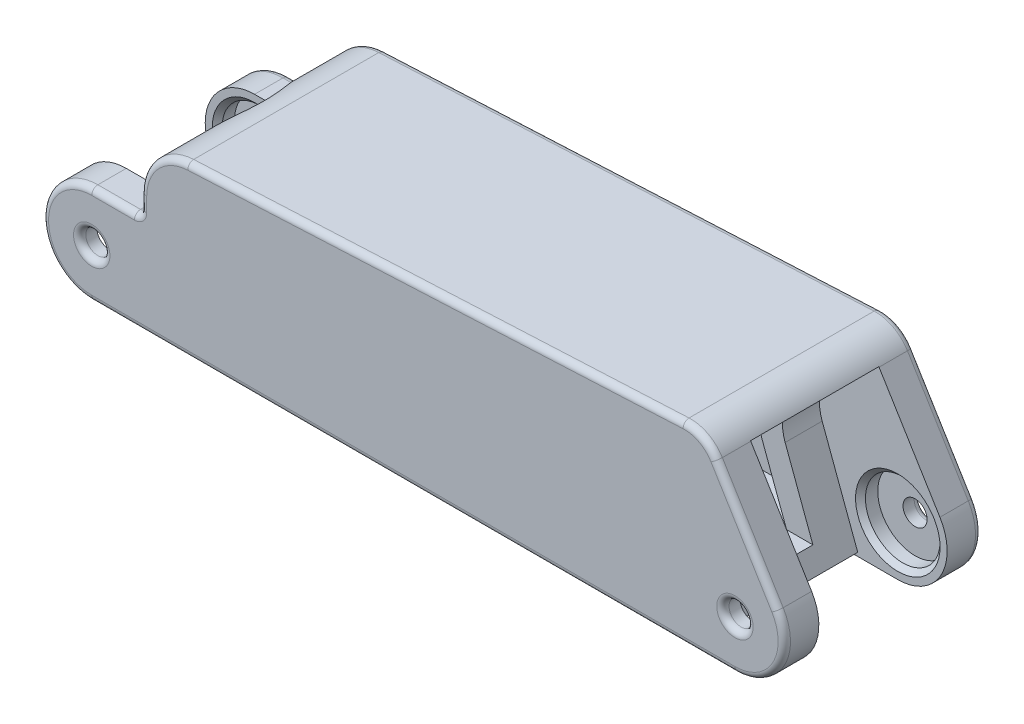
SolidWorks part; units mm, degrees
ref_plane "前视基准面" through (0, 0, 0) normal (0, 0, 1) x (1, 0, 0)
ref_plane "上视基准面" through (0, 0, 0) normal (0, 1, 0) x (1, 0, 0)
ref_plane "右视基准面" through (0, 0, 0) normal (1, 0, 0) x (0, 0, -1)
sketch "草图1" plane through (0, 0, 0) normal (0, 0, 1) x (1, 0, 0)
  line L10 (0, 0) -> (7.9583, 5.6673) construction
  line L11 (7.9583, 5.6673) -> (48.0618, 8.5912) construction
  line L12 (48.0618, 8.5912) -> (52.14, 0) construction
  line L13 (52.14, 0) -> (0, 0) construction
  line L14 (0, -4) -> (52.14, -4)
  line L15 (50.6217, 10.1555) -> (55.5531, 2.0858)
  line L16 (7.7667, 9.6627) -> (47.9182, 11.5878)
  line L20 (0, 4) -> (3.9583, 4)
  line L21 (3.9583, 5.6673) -> (3.9583, 4)
  arc A9 (0, 4) -> (0, -4) centre (0, 0) ccw
  arc A10 (7.7667, 9.6627) -> (3.9583, 5.6673) centre (7.9583, 5.6673) ccw
  arc A11 (50.6217, 10.1555) -> (47.9182, 11.5878) centre (48.0618, 8.5912) ccw
  arc A12 (52.14, -4) -> (55.5531, 2.0858) centre (52.14, 0) ccw
  dimension "D9" = 8
  dimension "D10" = 8
  dimension "D11" = 6
  dimension "D12" = 8
  dimension "D13" = 52.14
  dimension "D14" = 40.21
  dimension "D15" = 9.51
  dimension "D16" = 9.77
extrude "凸台-拉伸1" add sketch "草图1" along normal blind 8 and the other way blind 8
sketch "草图2" plane through (0, 0, 0) normal (0, 0, 1) x (1, 0, 0)
  line L0 (2.7297, -5.5668) -> (0, 0) construction
  line L1 (2.7297, -5.5668) -> (49.7599, 6.1592) construction
  line L2 (-1.5288, -3.6963) -> (0.0361, -6.8876)
  line L3 (-0.12, -22.8543) -> (51.9611, -22.8543) construction
  line L4 (-0.12, -22.8543) -> (12.3687, -25.0564) construction
  line L5 (55.5531, 2.0858) -> (50.6217, 10.1555) construction
  line L6 (3.9583, 4) -> (0, 4) construction
  line L7 (55.5531, 2.0858) -> (52.7003, 6.7541)
  line L8 (3.45, 4) -> (0, 4)
  line L11 (0, -4) -> (52.14, -4) construction
  line L12 (7.1667, -4) -> (52.14, -4)
  arc A0 (0.0361, -6.8876) -> (5.4785, -6.7683) centre (2.7297, -5.5668) ccw
  arc A2 (52.7003, 6.7541) -> (49.8235, 9.1585) centre (49.7599, 6.1592) ccw
  arc A3 (49.8235, 9.1585) -> (3.45, 4) centre (46.0635, -168.0616) ccw
  arc A4 (7.1667, -4) -> (5.4785, -6.7683) centre (16.474, -11.5745) ccw
  circle A6 centre (52.14, 0) radius 0.9969 construction
  arc A7 (52.14, -4) -> (55.5531, 2.0858) centre (52.14, 0) ccw construction
  arc A8 (52.14, -4) -> (55.5531, 2.0858) centre (52.14, 0) ccw
  arc A9 (0, 4) -> (-1.5288, -3.6963) centre (0, 0) ccw
  dimension "D2" = 6
  dimension "D3" = 6
  dimension "D6" = 24
  dimension "D7" = 177.26
  dimension "D8" = 0
  dimension "D11" = 6.6031
  dimension "D4" = 48.47
  dimension "D5" = 6.2
  dimension "D9" = 10
  dimension "D10" = 24
extrude "切除-拉伸1" cut sketch "草图2" against normal blind 2.2 and the other way blind 2.2
sketch "草图3" plane through (0, 0, 0) normal (0, 0, 1) x (1, 0, 0)
  circle A0 centre (0, 0) radius 0.975
  circle A1 centre (52.14, 0) radius 0.975
  dimension "D1" = 1.95
  dimension "D2" = 1.95
extrude "切除-拉伸2" cut sketch "草图3" against normal through all both and the other way through all
sketch "草图4" plane through (0, 4, 0) normal (0, 1, 0) x (1, 0, 0)
  line L0 (0, 0) -> (6, 0) construction
  line L5 (-2.9933, 5.2) -> (2.9933, 5.2)
  line L6 (-2.9933, -5.2) -> (2.9933, -5.2)
  line L7 (-2.9933, 5.2) -> (-6.8366, 5.2)
  line L8 (-6.8366, 5.2) -> (-6.8366, -5.2)
  line L9 (-6.8366, -5.2) -> (-2.9933, -5.2)
  arc A0 (-2.9933, 5.2) -> (-2.9933, -5.2) centre (0, 0) ccw construction
  arc A1 (2.9933, -5.2) -> (2.9933, 5.2) centre (0, 0) ccw
  dimension "D1" = 12
  dimension "D2" = 5.2
  dimension "D3" = 10.4
extrude "切除-拉伸5" cut sketch "草图4" against normal through all both and the other way through all
sketch "草图5" plane through (0, 0, 0) normal (0, 0, 1) x (1, 0, 0)
  line L0 (52.14, 0) -> (87.14, 0) construction
  line L1 (49.2899, 5.2799) -> (52.14, 0) construction
  line L2 (46.65, 3.8549) -> (49.5001, -1.425) construction
  line L4 (49.6265, 8.2609) -> (87.5888, 3.9747) construction
  line L5 (52.14, -4) -> (49.0005, -4)
  line L8 (46.21, 3.6173) -> (49.0601, -1.6625) construction
  line L11 (47.4649, 8.2664) -> (50.6039, 10.1846)
  line L12 (49.6826, 8.7578) -> (87.6449, 4.4716) construction
  line L13 (55.5531, 2.0858) -> (50.6217, 10.1555) construction
  line L14 (55.5531, 2.0858) -> (50.6039, 10.1846)
  line L17 (0, -4) -> (52.14, -4) construction
  line L18 (46.0086, 4.0622) -> (49.0005, -4)
  arc A0 (49.5001, -1.425) -> (52.0543, -2.9988) centre (52.14, 0) ccw construction
  arc A1 (49.6265, 8.2609) -> (46.65, 3.8549) centre (49.2899, 5.2799) ccw construction
  arc A2 (87.0257, -3.9984) -> (87.5888, 3.9747) centre (87.14, 0) ccw construction
  circle A3 centre (52.14, 0) radius 0.975 construction
  arc A4 (52.14, -4) -> (55.5531, 2.0858) centre (52.14, 0) ccw construction
  arc A5 (52.14, -4) -> (55.5531, 2.0858) centre (52.14, 0) ccw
  arc A6 (47.4649, 8.2664) -> (46.0086, 4.0622) centre (49.2899, 5.2799) ccw
  arc A9 (49.0601, -1.6625) -> (52.04, -3.4986) centre (52.14, 0) ccw construction
  arc A10 (49.6826, 8.7578) -> (46.21, 3.6173) centre (49.2899, 5.2799) ccw construction
  dimension "D2" = 6
  dimension "D3" = 6
  dimension "D4" = 8
  dimension "D7" = 0
  dimension "D1" = 6
  dimension "D5" = 35
  dimension "D6" = 118.36
  dimension "D9" = 8
  dimension "D8" = 0.5
extrude "切除-拉伸6" cut sketch "草图5" against normal blind 5.2 and the other way blind 5.2
sketch "草图6" plane through (0, 0, -5.2) normal (0, 0, 1) x (1, 0, 0)
  circle A0 centre (0, 0) radius 3.025
  dimension "D1" = 6.05
extrude "切除-拉伸7" cut sketch "草图6" against normal blind 1.4
sketch "草图7" plane through (0, 0, -5.2) normal (0, 0, 1) x (1, 0, 0)
  circle A0 centre (52.14, 0) radius 3.025
  dimension "D1" = 6.05
extrude "切除-拉伸8" cut sketch "草图7" against normal blind 1.4
sketch "草图9" plane through (0, 0, 2.2) normal (0, 0, -1) x (-1, 0, 0)
  line L10 (-7.5821, -2) -> (-7.5821, 2.9216)
  line L11 (-7.5821, -2) -> (-7.5821, 2.9216)
  line L12 (-44.1336, 3.3663) -> (-46.125, -2)
  line L13 (-46.125, -2) -> (-7.5821, -2)
  line L14 (-46.125, -2) -> (-7.5821, -2)
  line L15 (-44.1336, 3.3663) -> (-46.125, -2)
  arc A4 (-7.5821, 2.9216) -> (-44.1314, 7.1877) centre (-46.0635, -168.0616) ccw
  arc A5 (-44.1336, 3.3663) -> (-44.1314, 7.1877) centre (-49.2899, 5.2799) ccw
  arc A6 (-7.5821, 2.9216) -> (-44.1314, 7.1877) centre (-46.0635, -168.0616) ccw
  arc A7 (-44.1336, 3.3663) -> (-44.1314, 7.1877) centre (-49.2899, 5.2799) ccw
  dimension "D1" = 2
extrude "切除-拉伸10" cut sketch "草图9" against normal blind 3.2
mirror "镜向1" about plane through (0, 0, 0) normal (0, 0, 1) of "切除-拉伸10", "切除-拉伸7", "切除-拉伸8"
sketch "草图8" plane through (0, -4, 0) normal (0, -1, 0) x (1, 0, 0)
  line L0 (2.9933, -5.2) -> (0, -5.2) construction
  line L1 (0, 5.2) -> (15, 5.2)
  line L2 (0, 5.2) -> (0, -5.2)
  line L3 (0, -5.2) -> (15, -5.2)
  line L4 (15, 5.2) -> (15, -5.2)
  dimension "D1" = 15
extrude "切除-拉伸9" cut sketch "草图8" against normal blind 8.4
sketch "草图10" plane through (0, -4, 0) normal (0, -1, 0) x (1, 0, 0)
  line L0 (48.9515, -2.2) -> (5.5821, -2.2) construction
  line L1 (49.0005, 2.2) -> (24.0005, 2.2)
  line L2 (49.0005, 2.2) -> (49.0005, -2.2)
  line L3 (49.0005, -2.2) -> (24.0005, -2.2)
  line L4 (24.0005, 2.2) -> (24.0005, -2.2)
  line L5 (49.0005, 5.2) -> (49.0005, 2.2) construction
  point P7 (0, 0)
  dimension "D1" = 25
  dimension "D2" = 0
extrude "凸台-拉伸2" add sketch "草图10" against normal blind 2
sketch "草图11" plane through (0, 0, -2.2) normal (0, 0, -1) x (-1, 0, 0)
  line L3 (-49.0005, -2) -> (-49.0005, -4)
  line L4 (-49.0005, -4) -> (-48.2583, -2)
  line L5 (-48.2583, -2) -> (-49.0005, -2)
  line L6 (-49.0005, -2) -> (-49.0005, -4)
  line L7 (-49.0005, -4) -> (-48.2583, -2)
  line L8 (-48.2583, -2) -> (-49.0005, -2)
  dimension "D1" = 0
extrude "切除-拉伸11" cut sketch "草图11" against normal blind 4.5
fillet "圆角2" radius 0.5 24 edges at (26.07, -4, -8) (55.6288, -1.9566, -8) (53.0874, 6.1207, -8) (49.4662, 11.2422, -8) (27.8425, 10.6252, -8) (5.0629, 8.4272, -8) (3.9583, 4.8337, -8) (1.9791, 4, -8) (-4, 0, -8) (53.115, 0, -8) (0.975, 0, -8) (1.9791, 4, 8) (3.9583, 4.8337, 8) (5.0629, 8.4272, 8) (27.8425, 10.6252, 8) (49.4662, 11.2422, 8) (53.0874, 6.1207, 8) (55.6288, -1.9566, 8) (26.07, -4, 8) (-4, 0, 8) (53.115, 0, 8) (0.975, 0, 8) (3.9583, 4, 6.6) (3.9583, 4, -6.6)
chamfer "倒角1" distance 0.4 angle 45 5 edges at (55.165, 0, -5.2) (55.165, 0, 5.2) (3.025, 0, 5.2) (3.025, 0, -5.2) (49.0005, -4, 0) first distance on face at (55.165, 0, -5.2) first distance on face at (55.165, 0, 6.6) first distance on face at (3.025, 0, 6.6) first distance on face at (3.025, 0, -5.2) first distance on face at (25.9101, -4, 0)
fillet "圆角3" radius 1.5 6 edges at (15, -3, -5.2) (24.0005, -3, -2.2) (24.0005, -3, 2.2) (15, -3, 5.2) (15, -3, -2.2) (15, -3, 2.2)
